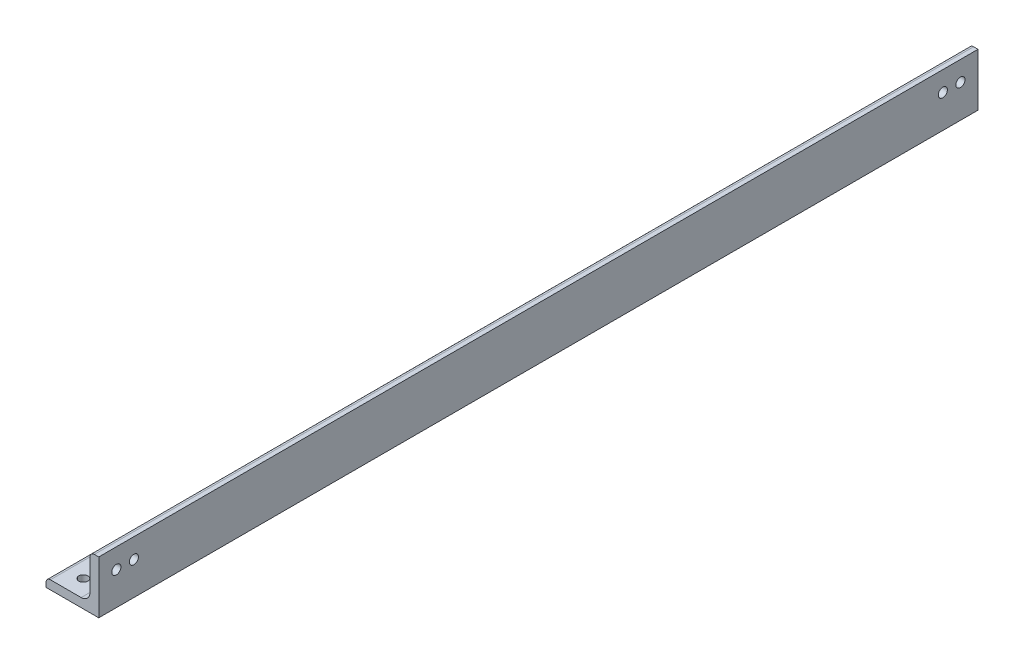
SolidWorks part; units mm, degrees
material "6061-T6 (SS)"
ref_plane "Front Plane" through (0, 0, 0) normal (0, 0, 1) x (1, 0, 0)
ref_plane "Top Plane" through (0, 0, 0) normal (0, 1, 0) x (1, 0, 0)
ref_plane "Right Plane" through (0, 0, 0) normal (1, 0, 0) x (0, 0, -1)
sketch "Sketch0" plane through (0, 0, 0) normal (0, 0, 1) x (1, 0, 0)
  line L0 (-9.525, -9.525) -> (9.525, -9.525)
  line L1 (9.525, -9.525) -> (9.525, 9.525)
  line L2 (9.525, 0) -> (0, 0) construction
  line L3 (0, 0) -> (0, -9.525) construction
  line L4 (6.35, -3.175) -> (6.35, 9.525) construction
  line L5 (3.175, -6.35) -> (-9.525, -6.35) construction
  arc A0 (6.35, -3.175) -> (3.175, -6.35) centre (3.175, -3.175) cw
  point P3 (5.4201, -5.4201)
  dimension "Inside Corner Radius" = 3.175
  dimension "Outside Height" = 19.05
  dimension "Inside Height" = 15.875
  dimension "Inside Width" = 15.875
  dimension "Wall Thickness" = 3.175
  dimension "D1" = 3.175
  dimension "Outside Width" = 19.05
sketch "Sketch1" plane through (0, 0, 0) normal (1, 0, 0) x (0, 0, -1)
  line L0 (158.75, 0) -> (-158.75, 0)
  point P4 (0, 0)
  dimension "Length" = 317.5
sketch "Sketch2" plane through (0, 0, 0) normal (0, 0, 1) x (1, 0, 0)
  line L0 (-9.525, -9.525) -> (9.525, -9.525)
  line L1 (9.525, -9.525) -> (9.525, 9.525)
  line L2 (9.525, 9.525) -> (6.35, 9.525) construction
  line L3 (6.35, 7.9375) -> (6.35, -3.175)
  line L4 (3.175, -6.35) -> (-7.9375, -6.35)
  line L5 (-9.525, -9.525) -> (-9.525, -6.35) construction
  line L6 (7.9375, 9.525) -> (9.525, 9.525)
  line L7 (-9.525, -7.9375) -> (-9.525, -9.525)
  line L8 (9.525, 0) -> (0, 0) construction
  line L9 (0, 0) -> (0, -9.525) construction
  arc A0 (6.35, 7.9375) -> (7.9375, 9.525) centre (7.9375, 7.9375) cw
  arc A1 (-9.525, -7.9375) -> (-7.9375, -6.35) centre (-7.9375, -7.9375) cw
  arc A2 (6.35, -3.175) -> (3.175, -6.35) centre (3.175, -3.175) cw
  dimension "Inside Radius" = 3.175
  dimension "Height" = 19.05
  dimension "Width" = 19.05
  dimension "Thickness" = 3.175
extrude "Boss-Extrude1" add sketch "Sketch2" along normal mid plane 317.5
sketch "Break Locations" plane through (0, 0, 0) normal (1, 0, 0) x (0, 0, -1)
  line L0 (-139.319, 0) -> (139.319, 0)
  line L1 (-158.75, -9.525) -> (-158.75, 9.525) construction
  line L2 (158.75, -9.525) -> (158.75, 9.525) construction
  point P0 (-142.5575, 0)
  point P1 (142.5575, 0)
  point P10 (0, 0)
  point P11 (139.319, 0)
  point P13 (-139.319, 0)
  dimension "D1" = 16.1925
  dimension "D2" = 16.1925
  dimension "D3" = 19.431
sketch "Sketch3" plane through (0, -6.35, 0) normal (0, 1, 0) x (1, 0, 0)
  line L0 (-2.3812, 158.75) -> (-2.3812, 152.4) construction
  line L1 (3.175, 158.75) -> (-7.9375, 158.75) construction
  line L2 (-2.3812, 152.4) -> (-2.3812, 146.05) construction
  line L3 (3.175, 0) -> (-7.9375, 0) construction
  line L4 (3.175, -158.75) -> (3.175, 158.75) construction
  line L5 (-7.9375, -158.75) -> (-7.9375, 158.75) construction
  circle A0 centre (-2.3812, 152.4) radius 1.651
  circle A1 centre (-2.3812, 146.05) radius 1.651
  circle A2 centre (-2.3812, -146.05) radius 1.651
  circle A3 centre (-2.3812, -152.4) radius 1.651
  dimension "D2" = 3.302
  dimension "D4" = 3.302
  dimension "D1" = 6.35
  dimension "D3" = 6.35
extrude "Cut-Extrude1" cut sketch "Sketch3" against normal through all
sketch "Sketch4" plane through (6.35, 0, 0) normal (-1, 0, 0) x (0, 0, 1)
  line L0 (-158.75, 2.3813) -> (-152.4, 2.3813) construction
  line L1 (-152.4, 2.3813) -> (-146.05, 2.3813) construction
  line L2 (0, 7.9375) -> (0, -3.175) construction
  line L3 (-158.75, 7.9375) -> (-158.75, -3.175) construction
  line L4 (158.75, 7.9375) -> (-158.75, 7.9375) construction
  line L5 (158.75, -3.175) -> (-158.75, -3.175) construction
  circle A0 centre (-152.4, 2.3813) radius 1.651
  circle A1 centre (-146.05, 2.3813) radius 1.651
  circle A2 centre (146.05, 2.3813) radius 1.651
  circle A3 centre (152.4, 2.3813) radius 1.651
  dimension "D1" = 3.302
  dimension "D3" = 3.302
  dimension "D2" = 6.35
  dimension "D4" = 6.35
  dimension "D5" = 90
  dimension "D6" = 180
extrude "Cut-Extrude2" cut sketch "Sketch4" against normal through all
sketch "Sketch5" plane through (6.35, 0, 0) normal (-1, 0, 0) x (0, 0, 1)
  line L0 (-146.05, 2.3813) -> (-127, 2.3813) construction
  line L2 (-127, 5.5563) -> (-99.06, 5.5563)
  line L3 (-127, -0.7937) -> (-99.06, -0.7937)
  arc A0 (-127, 5.5563) -> (-127, -0.7937) centre (-127, 2.3813) ccw
  arc A1 (-99.06, -0.7937) -> (-99.06, 5.5563) centre (-99.06, 2.3813) ccw
  dimension "D1" = 3.175
  dimension "D3" = 3.175
  dimension "D2" = 27.94
  dimension "D4" = 19.05
equation "\"D1@Break Locations\" = .85 * \"Height@Sketch2\""
equation "\"D2@Break Locations\"=\"D1@Break Locations\""
equation "\"Thickness@Sketch2\"=\"wall thickness@sketch0\""
equation "\"Height@Sketch2\"=\"outside height@sketch0\""
equation "\"Width@Sketch2\"=\"outside width@sketch0\""
equation "\"Inside Radius@Sketch2\"=\"inside corner radius@sketch0\""
equation "\"Length@Boss-Extrude1\"=\"length@sketch1\""
equation "\"D3@Break Locations\"=\"D2@Break Locations\"*1.2"
equation "\"D1@Sketch0\"=\"Wall Thickness@Sketch0\""
